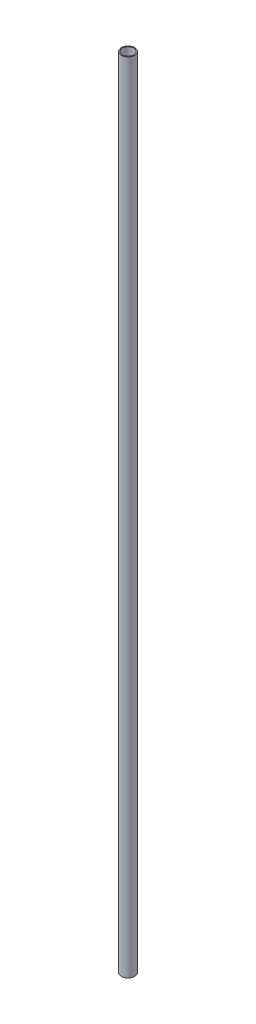
SolidWorks part; units mm, degrees
material "AISI Type 316L stainless steel"
ref_plane "Front Plane" through (0, 0, 0) normal (0, 0, 1) x (1, 0, 0)
ref_plane "Top Plane" through (0, 0, 0) normal (0, 1, 0) x (1, 0, 0)
ref_plane "Right Plane" through (0, 0, 0) normal (1, 0, 0) x (0, 0, -1)
sketch "Sketch1" plane through (0, 0, 0) normal (0, 1, 0) x (1, 0, 0)
  circle A0 centre (0, 0) radius 6.5
  circle A1 centre (0, 0) radius 7.5
  dimension "D1" = 15
  dimension "D2" = 1
extrude "Boss-Extrude1" add sketch "Sketch1" against normal blind 890
